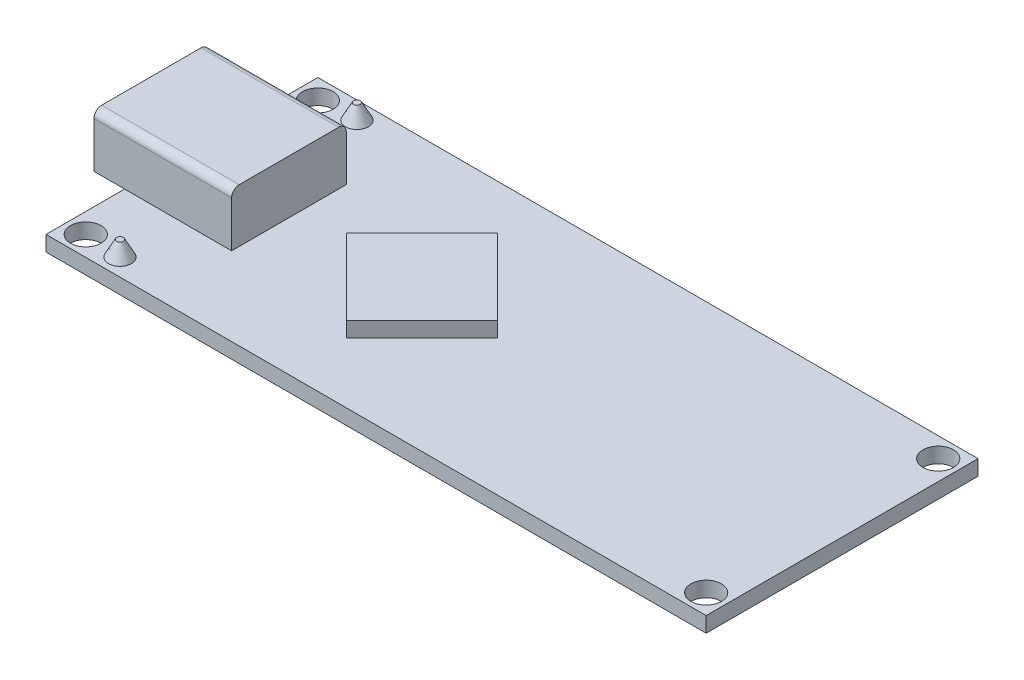
SolidWorks part; units mm, degrees
ref_plane "Plano frontal" through (0, 0, 0) normal (0, 0, 1) x (1, 0, 0)
ref_plane "Plano superior" through (0, 0, 0) normal (0, 1, 0) x (1, 0, 0)
ref_plane "Plano direito" through (0, 0, 0) normal (1, 0, 0) x (0, 0, -1)
sketch "Esboço1" plane through (0, 0, 0) normal (0, 1, 0) x (1, 0, 0)
  line L1 (-21.59, -8.89) -> (21.59, -8.89)
  line L2 (-21.59, -8.89) -> (-21.59, 8.89)
  line L3 (-21.59, 8.89) -> (21.59, 8.89)
  line L4 (21.59, -8.89) -> (21.59, 8.89)
  line L5 (-21.59, -8.89) -> (21.59, 8.89) construction
  line L6 (-21.59, 8.89) -> (21.59, -8.89) construction
  point P0 (0, 0)
  dimension "D1" = 43.18
  dimension "D2" = 17.78
extrude "Ressalto-extrusão1" add sketch "Esboço1" along normal blind 1
sketch "Esboço2" plane through (0, 0, 0) normal (0, -1, 0) x (1, 0, 0)
  line L0 (-21.59, -8.89) -> (-21.59, 8.89) construction
  line L1 (-18.89, 8.75) -> (-16.89, 8.75)
  line L2 (-18.89, 8.75) -> (-18.89, 6.75)
  line L3 (-18.89, 6.75) -> (-16.89, 6.75)
  line L4 (-16.89, 8.75) -> (-16.89, 6.75)
  line L5 (-18.89, 8.75) -> (-16.89, 6.75) construction
  line L6 (-18.89, 6.75) -> (-16.89, 8.75) construction
  line L7 (-18.89, -6.75) -> (-16.89, -6.75)
  line L8 (-18.89, -6.75) -> (-18.89, -8.75)
  line L9 (-18.89, -8.75) -> (-16.89, -8.75)
  line L10 (-16.89, -6.75) -> (-16.89, -8.75)
  line L11 (-18.89, -6.75) -> (-16.89, -8.75) construction
  line L12 (-18.89, -8.75) -> (-16.89, -6.75) construction
  line L13 (-16.89, -8.75) -> (-16.89, -8.89) construction
  line L14 (21.59, -8.89) -> (-21.59, -8.89) construction
  line L15 (-16.89, 8.75) -> (-16.89, 8.89) construction
  line L16 (-21.59, 8.89) -> (21.59, 8.89) construction
  point P0 (-17.89, 7.75)
  point P5 (-17.89, -7.75)
  dimension "D1" = 2
  dimension "D2" = 13.5
  dimension "D3" = 2.7
extrude "Ressalto-extrusão2" [suppressed] add sketch "Esboço2" against normal blind 2 from surface
sketch "Esboço3" [suppressed] plane through (0, 3, 0) normal (0, 1, 0) x (-1, 0, 0)
  line L1 (17.39, 8.25) -> (18.39, 8.25)
  line L2 (17.39, 8.25) -> (17.39, 7.25)
  line L3 (17.39, 7.25) -> (18.39, 7.25)
  line L4 (18.39, 8.25) -> (18.39, 7.25)
  line L5 (17.39, 8.25) -> (18.39, 7.25) construction
  line L6 (17.39, 7.25) -> (18.39, 8.25) construction
  line L7 (17.39, -8.25) -> (18.39, -8.25)
  line L8 (17.39, -8.25) -> (17.39, -7.25)
  line L9 (17.39, -7.25) -> (18.39, -7.25)
  line L10 (18.39, -8.25) -> (18.39, -7.25)
  line L11 (17.39, -8.25) -> (18.39, -7.25) construction
  line L12 (17.39, -7.25) -> (18.39, -8.25) construction
  point P0 (17.89, 7.75)
  point P6 (17.89, -7.75)
  dimension "D1" = 1
extrude "Ressalto-extrusão3" [suppressed] add sketch "Esboço3" along normal blind 6
sketch "Esboço5" plane through (0, 1, 0) normal (0, 1, 0) x (1, 0, 0)
  line L0 (-18.89, 8.75) -> (-16.89, 6.75) construction
  circle A0 centre (-17.89, 7.75) radius 0.75
  circle A1 centre (-17.89, -7.75) radius 0.75
  dimension "D1" = 1.5
extrude "Ressalto-extrusão5" add sketch "Esboço5" along normal blind 1 draft 28
chamfer "Chanfro1" [suppressed] distance 0.3 angle 45
pattern_linear "Padrão linear1" [suppressed] count 15 spacing 2.555 of bodies 106
sketch "Esboço4" plane through (0, 1, 0) normal (0, 1, 0) x (1, 0, 0)
  line L0 (-10.8397, 0) -> (-5.89, 4.9497)
  line L1 (-5.89, 4.9497) -> (-0.9403, 0)
  line L2 (-0.9403, 0) -> (-5.89, -4.9497)
  line L3 (-5.89, -4.9497) -> (-10.8397, 0)
  line L4 (-5.89, 4.9497) -> (-5.89, 8.89) construction
  line L5 (21.59, 8.89) -> (-21.59, 8.89) construction
  line L6 (-5.89, -4.9497) -> (-5.89, -8.89) construction
  line L7 (-21.59, -8.89) -> (21.59, -8.89) construction
  line L8 (-21.59, 8.89) -> (-21.59, -8.89) construction
  dimension "D1" = 7
  dimension "D2" = 15.7
extrude "Ressalto-extrusão4" add sketch "Esboço4" along normal blind 1
sketch "Esboço6" plane through (0, 1, 0) normal (0, 1, 0) x (1, 0, 0)
  line L0 (-23.59, 0) -> (-21.59, 0) construction
  line L1 (-14.59, 3.75) -> (-23.59, 3.75)
  line L2 (-14.59, 3.75) -> (-14.59, -3.75)
  line L3 (-14.59, -3.75) -> (-23.59, -3.75)
  line L4 (-23.59, 3.75) -> (-23.59, -3.75)
  line L5 (-21.59, 8.89) -> (-21.59, -8.89) construction
  dimension "D1" = 7.5
  dimension "D2" = 9
  dimension "D3" = 2
extrude "Ressalto-extrusão6" add sketch "Esboço6" along normal blind 3.5
sketch "Esboço7" plane through (0, 1, 0) normal (0, 1, 0) x (1, 0, 0)
  line L0 (-20.29, 7.59) -> (20.29, 7.59) construction
  line L1 (20.29, 7.59) -> (20.29, -7.59) construction
  line L2 (20.29, -7.59) -> (-20.29, -7.59) construction
  line L3 (-20.29, -7.59) -> (-20.29, 7.59) construction
  line L4 (-20.29, 7.59) -> (20.29, -7.59) construction
  line L5 (21.59, 8.89) -> (-21.59, 8.89) construction
  line L6 (-21.59, 8.89) -> (-21.59, 3.75) construction
  circle A0 centre (-20.29, 7.59) radius 1
  circle A1 centre (-20.29, -7.59) radius 1
  circle A2 centre (20.29, -7.59) radius 1
  circle A3 centre (20.29, 7.59) radius 1
  dimension "D1" = 2
  dimension "D2" = 1.3
  dimension "D3" = 1.3
extrude "Corte-extrusão1" cut sketch "Esboço7" against normal through all
sketch "Esboço8" plane through (-23.59, 0, 0) normal (-1, 0, 0) x (0, 0, 1)
  line L0 (-3.75, 4.5) -> (3.75, 1) construction
  line L1 (-3.75, 4.5) -> (3.75, 4.5) construction
  line L2 (-3.25, 1.5) -> (3.25, 1.5)
  line L3 (-3.25, 1.5) -> (-3.25, 4)
  line L4 (-3.25, 4) -> (3.25, 4)
  line L5 (3.25, 1.5) -> (3.25, 4)
  line L6 (-3.25, 1.5) -> (3.25, 4) construction
  line L7 (-3.25, 4) -> (3.25, 1.5) construction
  line L8 (3.75, 4.5) -> (3.75, 1) construction
  line L10 (2.5, 2.25) -> (-2.5, 2.25)
  line L11 (2.5, 2.25) -> (2.5, 3.25)
  line L12 (2.5, 3.25) -> (-2.5, 3.25)
  line L13 (-2.5, 2.25) -> (-2.5, 3.25)
  line L14 (2.5, 2.25) -> (-2.5, 3.25) construction
  line L15 (2.5, 3.25) -> (-2.5, 2.25) construction
  point P4 (0, 2.75)
  point P13 (0, 2.75)
  dimension "D1" = 0.5
  dimension "D2" = 0.5
  dimension "D3" = 5
  dimension "D4" = 1
extrude "Corte-extrusão2" cut sketch "Esboço8" against normal blind 7
sketch "Esboço10" plane through (0, 1, 0) normal (0, 1, 0) x (1, 0, 0)
  line L0 (21.39, 0) -> (21.59, 0) construction
  line L1 (16.89, 1) -> (21.39, 1)
  line L2 (16.89, 1) -> (16.89, -1)
  line L3 (16.89, -1) -> (21.39, -1)
  line L4 (21.39, 1) -> (21.39, -1)
  line L5 (21.59, -8.89) -> (21.59, 8.89) construction
  dimension "D1" = 2
  dimension "D2" = 0.2
  dimension "D3" = 4.5
extrude "Ressalto-extrusão7" [suppressed] add sketch "Esboço10" along normal blind 2
sketch "Esboço11" [suppressed] plane through (0, 3, 0) normal (0, 1, 0) x (1, 0, 0)
  line L0 (17.37, 0.5) -> (18.37, -0.5) construction
  line L1 (17.37, 0.5) -> (18.37, 0.5)
  line L2 (17.37, 0.5) -> (17.37, -0.5)
  line L3 (17.37, -0.5) -> (18.37, -0.5)
  line L4 (18.37, 0.5) -> (18.37, -0.5)
  line L5 (19.91, 0.5) -> (20.91, 0.5)
  line L6 (19.91, 0.5) -> (19.91, -0.5)
  line L7 (19.91, -0.5) -> (20.91, -0.5)
  line L8 (20.91, 0.5) -> (20.91, -0.5)
  line L9 (20.91, -0.5) -> (19.91, 0.5) construction
  line L10 (17.87, 0) -> (20.41, 0) construction
  line L11 (19.14, -1) -> (19.14, 1) construction
  line L12 (16.89, -1) -> (21.39, -1) construction
  line L13 (21.39, 1) -> (16.89, 1) construction
  point P16 (19.14, 0)
  dimension "D1" = 2.54
  dimension "D2" = 1
extrude "Ressalto-extrusão8" [suppressed] add sketch "Esboço11" along normal blind 6
chamfer "Chanfro2" [suppressed] distance 0.3 angle 45
pattern_linear "Padrão linear2" [suppressed] count 2 spacing 2.54 count 2 spacing 2.54 of bodies 111
fillet "Filete1" radius 0.5 2 edges at (-19.09, 4.5, -3.75) (-19.09, 4.5, 3.75)
